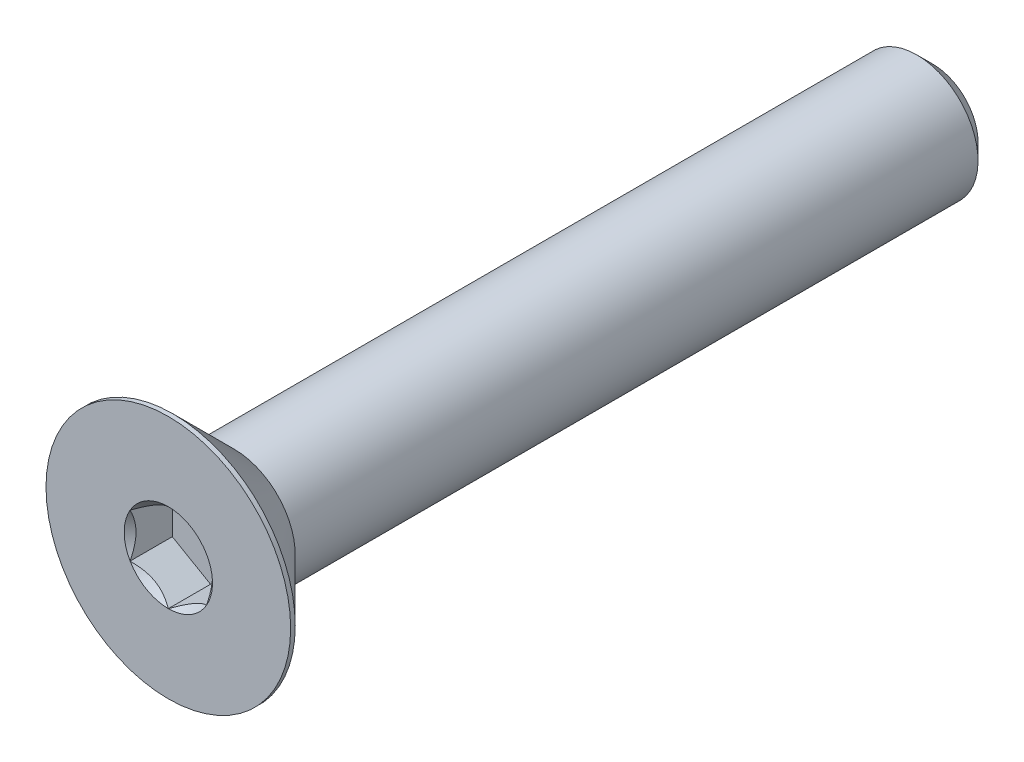
SolidWorks part; units mm, degrees
ref_plane "Front" through (0, 0, 0) normal (0, 0, 1) x (1, 0, 0)
ref_plane "Top" through (0, 0, 0) normal (0, 1, 0) x (1, 0, 0)
ref_plane "Right" through (0, 0, 0) normal (1, 0, 0) x (0, 0, -1)
sketch "Sketch1" plane through (0, 0, 0) normal (0, 0, 1) x (1, 0, 0)
  line L1 (1.25, 0.7217) -> (0, 1.4434)
  line L8 (0, 1.4434) -> (-1.25, 0.7217)
  line L9 (-1.25, 0.7217) -> (-1.25, -0.7217)
  line L10 (-1.25, -0.7217) -> (0, -1.4434)
  line L11 (0, -1.4434) -> (1.25, -0.7217)
  line L12 (1.25, -0.7217) -> (1.25, 0.7217)
  circle A0 centre (0, 0) radius 1.25 construction
  circle A1 centre (0, 0) radius 4
  point P7 (0, 4)
  dimension "Head Dia" = 8
  dimension "Hex" = 2.5
sketch "Sketch2" plane through (0, 0, 0) normal (1, 0, 0) x (0, 0, -1)
  line L6 (0, 0) -> (22.7, 0) construction
  line L8 (22.7, 0) -> (22.7, 2)
  line L9 (22.7, 2) -> (0, 2)
  line L11 (0, 2) -> (0, 0)
  line L13 (0, 2) -> (-0.15, 2)
  line L14 (-0.15, 2) -> (-2.15, 4)
  line L15 (-2.15, 4) -> (-2.3, 4)
  line L16 (-2.3, 4) -> (-2.3, 0)
  line L17 (-2.3, 0) -> (0, 0)
  line L18 (22.7, -2) -> (0, -2)
  line L19 (-2.15, -4) -> (-2.3, -4)
  line L20 (22.6562, 2.0758) -> (23.0063, 1.4696) construction
  line L21 (23.0063, 1.4696) -> (23.3562, 2.0758) construction
  line L22 (23.3562, 2.0758) -> (22.6562, 2.0758) construction
  line L23 (22.6781, 2.0379) -> (23.3344, 2.0379)
  line L24 (23.3344, 2.0379) -> (23.05, 1.5453)
  line L25 (23.05, 1.5453) -> (22.9625, 1.5453)
  line L26 (22.9625, 1.5453) -> (22.6781, 2.0379)
  line L27 (23.0062, 1.5453) -> (23.0063, 1.4696) construction
  line L28 (22.7, 2) -> (23.3125, 2) construction
  line L29 (23.0062, 2.0758) -> (23.0062, 2) construction
  line L30 (22.175, 2) -> (22.7, 1.475)
  point P26 (-0.92, 0)
  point P31 (6.7, -4)
  point P32 (7.7, -4)
  point P33 (13.7, -4)
  point P38 (20.95, -2)
  point P51 (23.0062, 2.0379)
  point P53 (-2.3, 4)
  dimension "Dia" = 4
  dimension "Head Ht" = 2.3
  dimension "D1" = 45
  dimension "Lg" = 25
  dimension "Hex Depth" = 1.38
  dimension "D2" = 9
  dimension "D3" = 10
  dimension "D4" = 9
  dimension "Pitch" = 0.7
  dimension "D6" = 0.0875
  dimension "D5" = 45
  dimension "D7" = 0.525
  dimension "D8" = 1.75
sketch "Sketch14" plane through (0, 0, 0) normal (1, 0, 0) x (0, 0, -1)
  line L4 (-2.3, 0) -> (-2.3, 4)
  line L5 (-2.3, 4) -> (-2.15, 4)
  line L6 (-2.15, 4) -> (-0.15, 2)
  line L7 (-0.15, 2) -> (0, 2)
  line L8 (0, 2) -> (22.175, 2)
  line L9 (22.175, 2) -> (22.7, 1.475)
  line L10 (22.7, 1.475) -> (22.7, 0)
  line L11 (22.7, 0) -> (-2.3, 0)
revolve "Revolve1" add sketch "Sketch14" angle 360 about L11
cosmetic thread "Cosmetic Thread1" parameters "D2"=3
sketch "Sketch3" plane through (0, 0, -22.7) normal (0, 0, -1) x (-1, 0, 0)
  circle A0 centre (0, 0) radius 2
sketch "Sketch4" plane through (0, 0, 0) normal (1, 0, 0) x (0, 0, -1)
  line L0 (22.6781, 2.0379) -> (23.3344, 2.0379) construction
  line L1 (22.9625, 1.5453) -> (22.6781, 2.0379) construction
  line L2 (23.05, 1.5453) -> (22.9625, 1.5453) construction
  line L3 (23.3344, 2.0379) -> (23.05, 1.5453) construction
  line L4 (22.6781, 2.0379) -> (23.3344, 2.0379)
  line L5 (22.9625, 1.5453) -> (22.6781, 2.0379)
  line L6 (23.05, 1.5453) -> (22.9625, 1.5453)
  line L7 (23.3344, 2.0379) -> (23.05, 1.5453)
sketch "Sketch5" plane through (0, 0, 2.3) normal (0, 0, 1) x (1, 0, 0)
  line L0 (0, -1.4434) -> (1.25, -0.7217) construction
  line L1 (-1.25, -0.7217) -> (0, -1.4434) construction
  line L2 (-1.25, 0.7217) -> (-1.25, -0.7217) construction
  line L3 (0, 1.4434) -> (-1.25, 0.7217) construction
  line L4 (1.25, 0.7217) -> (0, 1.4434) construction
  line L5 (1.25, -0.7217) -> (1.25, 0.7217) construction
  line L6 (0, -1.4434) -> (1.25, -0.7217)
  line L7 (-1.25, -0.7217) -> (0, -1.4434)
  line L8 (-1.25, 0.7217) -> (-1.25, -0.7217)
  line L9 (0, 1.4434) -> (-1.25, 0.7217)
  line L10 (1.25, 0.7217) -> (0, 1.4434)
  line L11 (1.25, -0.7217) -> (1.25, 0.7217)
extrude "Cut-Extrude2" cut sketch "Sketch5" against normal up to vertex (1.38 mm away) up to point (0, 0, 0.92)
sketch "Sketch6" plane through (0, 0, 2.3) normal (0, 0, 1) x (1, 0, 0)
  circle A0 centre (0, 0) radius 1.4434
extrude "Cut-Extrude3" cut sketch "Sketch6" against normal up to vertex (1.38 mm away) draft 45 up to point (0, 0, 0.92)
split "Split1" [suppressed] bodies to split 134
curve "Helix/Spiral1" [suppressed] pitch 0.7 height 23.4 turns 33.4286
sweep "Cut-Sweep1" [suppressed] cut profiles "Sketch4" path "Helix/Spiral1"
sketch "Sketch15" plane through (0, 0, 0) normal (0, 0, 1) x (1, 0, 0)
  circle A2 centre (0, 0) radius 2
extrude "Boss-Extrude1" [suppressed] add sketch "Sketch15" against normal up to vertex draft 30.9
equation "\"D3@Helix/Spiral1\" =  ( \"Lg@Sketch2\" - \"Head Ht@Sketch2\" )  + \"Pitch@Sketch2\""
equation "\"D1\"= \"Head Ht@Sketch2\" * .7"
equation "\"D1\"= \"D1\""
equation "\"D4@Helix/Spiral1\" = \"Pitch@Sketch2\""
equation "\"Hex Depth@Sketch2\" = \"Head Ht@Sketch2\" * 0.6"
equation "\"D2@Sketch2\" = \"Head Dia@Sketch1\" * 1.125"
equation "\"D3@Sketch2\" = \"Head Dia@Sketch1\" * 1.25"
equation "\"D4@Sketch2\" = \"D2@Sketch2\""
equation "\"D6@Sketch2\" = \"Pitch@Sketch2\" / 8"
equation "\"D7@Sketch2\" = \"Pitch@Sketch2\" * 0.75"
equation "\"D8@Sketch2\" = \"Pitch@Sketch2\" * 2.5"
